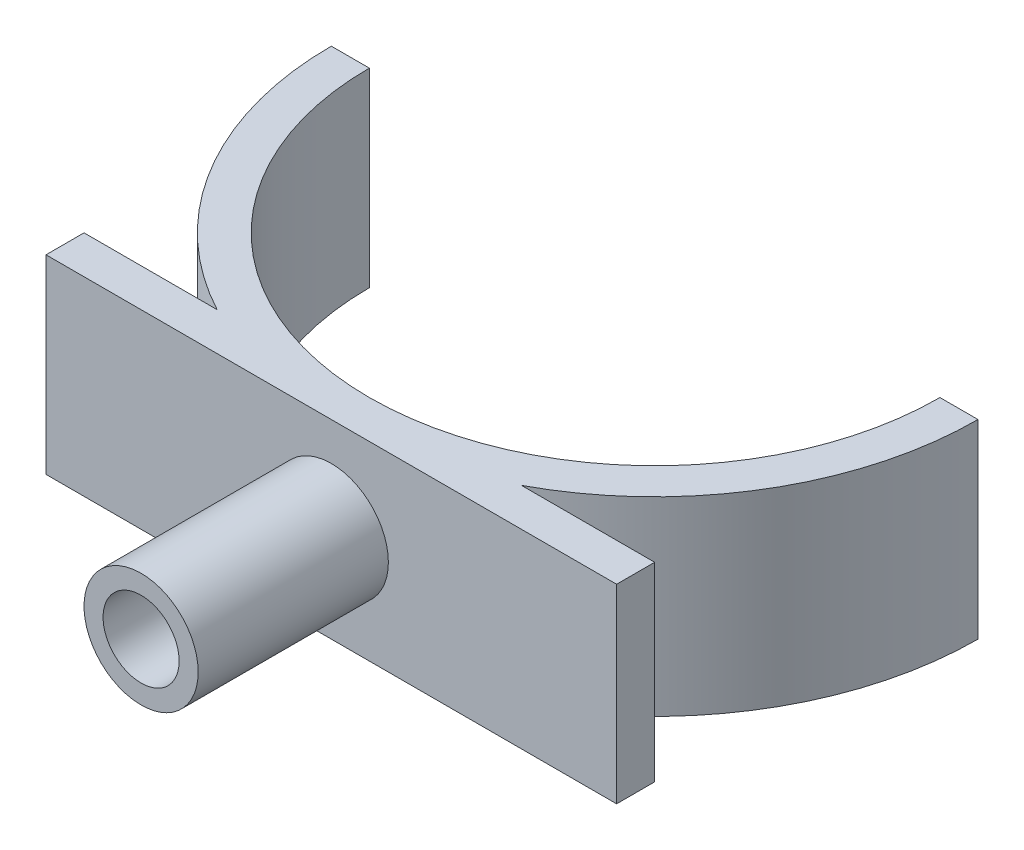
SolidWorks part; units mm, degrees
ref_plane "Alzado" through (0, 0, 0) normal (0, 0, 1) x (1, 0, 0)
ref_plane "Planta" through (0, 0, 0) normal (0, 1, 0) x (1, 0, 0)
ref_plane "Vista lateral" through (0, 0, 0) normal (1, 0, 0) x (0, 0, -1)
sketch "Sketch1" plane through (0, 0, 0) normal (0, 0, 1) x (1, 0, 0)
  circle A0 centre (0, 0) radius 2
  circle A1 centre (0, 0) radius 3
extrude "Boss-Extrude1" add sketch "Sketch1" along normal blind 10
ref_plane "Plane1" through (0, 0, 0) normal (0, 0, -1) x (-1, 0, 0)
sketch "Sketch2" plane through (0, 0, 0) normal (0, 0, -1) x (-1, 0, 0)
  line L19 (0, 5) -> (15, 5)
  line L20 (0, 5) -> (-15, 5)
  line L21 (-15, 5) -> (-15, -5)
  line L22 (-15, -5) -> (15, -5)
  line L23 (15, -5) -> (15, 5)
extrude "Boss-Extrude2" add sketch "Sketch2" along normal blind 2
sketch "Sketch4" plane through (0, 0, 0) normal (0, 1, 0) x (1, 0, 0)
  line L0 (-8, 2) -> (8, 2)
  line L3 (-17, 17) -> (-15, 17)
  line L4 (15, 17) -> (17, 17)
  line L5 (-8, 2) -> (8, 2)
  arc A2 (-15, 17) -> (15, 17) centre (0, 17) ccw
  arc A3 (8, 2) -> (17, 17) centre (0, 17) ccw
  arc A4 (-17, 17) -> (-8, 2) centre (0, 17) ccw
extrude "Boss-Extrude3" add sketch "Sketch4" along normal blind 5 and the other way blind 5 contours L3 A4 L0 A2 | L5 A3 L4 A2 region at (-14.383, 0, -8.3702) region at (10.7669, 0, -6.2331)
